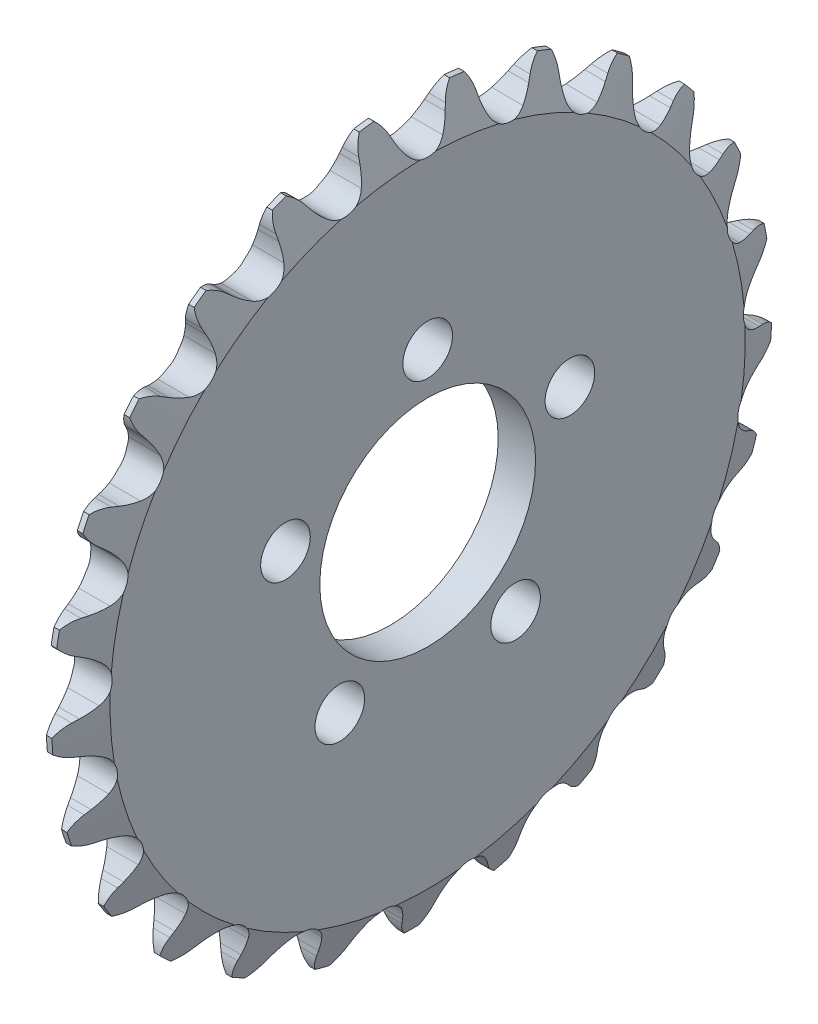
SolidWorks part; units mm, degrees
material "Alloy Steel"
ref_plane "Front Plane" through (0, 0, 0) normal (0, 0, 1) x (1, 0, 0)
ref_plane "Top Plane" through (0, 0, 0) normal (0, 1, 0) x (1, 0, 0)
ref_plane "Right Plane" through (0, 0, 0) normal (1, 0, 0) x (0, 0, -1)
ref_axis "X AXIS" through (-88.99, 0, 0) along (1, 0, 0)
ref_axis "Y AXIS" through (0, -55, 0) along (0, 1, 0)
ref_axis "Z AXIS" through (0, 0, 55) along (0, 0, -1)
other "Freeze***"
sketch "Sketch1" plane through (0, 0, 0) normal (1, 0, 0) x (0, 0, -1)
  line L0 (0, 25.3325) -> (-6.2999, 24.5366) construction
  line L1 (-1.9346, 25.3368) -> (-2.0951, 25.7414)
  line L2 (-1.9346, 25.3368) -> (2.0985, 26.9369) construction
  line L3 (2.0985, 26.9369) -> (0, 25.3325) construction
  line L4 (0, 25.3325) -> (-1.9329, 25.3325) construction
  line L5 (-3.4326, 27.1722) -> (-3.15, 24.9345) construction
  line L6 (0, 25.3325) -> (0, 23.6351) construction
  circle A0 centre (0, 0) radius 25.3325 construction
  arc A1 (-1.3484, 24.3015) -> (0, 23.6351) centre (0, 25.3325) ccw
  arc A2 (-1.3484, 24.3015) -> (-1.9346, 25.3368) centre (2.0985, 26.9369) cw
  arc A3 (-2.0951, 25.7414) -> (-3.4326, 27.1722) centre (-4.5863, 24.7531) ccw
sketch "Sketch2" plane through (0, 0, 0) normal (0, 0, 1) x (1, 0, 0)
  line L0 (0, 0) -> (0, 26.92) construction
  line L1 (-0.2064, 26.92) -> (0.2064, 26.92)
  line L2 (0.2064, 26.92) -> (1.397, 23.745)
  line L3 (1.397, 23.745) -> (1.397, 0)
  line L4 (-1.397, 0) -> (1.397, 0)
  line L5 (-1.397, 23.745) -> (-1.397, 0)
  line L6 (-0.2064, 26.92) -> (-1.397, 23.745)
  dimension "D1" = 26.92
  dimension "D2" = 2.794
revolve "Revolve1" add sketch "Sketch2" angle 360 about L4
sketch "Sketch3" plane through (0, 0, 0) normal (1, 0, 0) x (0, 0, -1)
  line L0 (-1.9346, 25.3368) -> (-2.0951, 25.7414) construction
  line L1 (-1.9346, 25.3368) -> (-2.0951, 25.7414)
  line L2 (0, 23.6351) -> (0, 0) construction
  line L3 (1.9346, 25.3368) -> (2.0951, 25.7414)
  arc A0 (-2.0951, 25.7414) -> (-3.4326, 27.1722) centre (-4.5863, 24.7531) ccw construction
  arc A1 (-1.9346, 25.3368) -> (-1.3484, 24.3015) centre (2.0985, 26.9369) ccw construction
  arc A2 (-1.3484, 24.3015) -> (0, 23.6351) centre (0, 25.3325) ccw construction
  arc A3 (-2.0951, 25.7414) -> (-3.4326, 27.1722) centre (-4.5863, 24.7531) ccw
  arc A4 (-1.9346, 25.3368) -> (-1.3484, 24.3015) centre (2.0985, 26.9369) ccw
  arc A5 (-1.3484, 24.3015) -> (1.3484, 24.3015) centre (0, 25.3325) ccw
  arc A6 (1.9346, 25.3368) -> (1.3484, 24.3015) centre (-2.0985, 26.9369) cw
  arc A7 (2.0951, 25.7414) -> (3.4326, 27.1722) centre (4.5863, 24.7531) cw
  arc A8 (-3.4326, 27.1722) -> (3.4326, 27.1722) centre (0, 0) cw
extrude "Cut-Extrude1" cut sketch "Sketch3" against normal through all both and the other way through all contours A8 A3 L1 A4 A5 A6 L3 A7 region at (0, 25.8551, 0)
pattern_circular "CirPattern1" count 25 over 360 about axis through (-88.99, 0, 0) along (1, 0, 0) of "Cut-Extrude1"
sketch "Sketch4" plane through (1.397, 0, 0) normal (1, 0, 0) x (0, 0, -1)
  line L0 (0, 0) -> (0, 11.176) construction
  circle A0 centre (0, 0) radius 8.0645
  circle A1 centre (0, 11.176) radius 1.8542
  circle A2 centre (10.629, 3.4536) radius 1.8542
  circle A3 centre (6.5691, -9.0416) radius 1.8542
  circle A4 centre (-6.5691, -9.0416) radius 1.8542
  circle A5 centre (-10.629, 3.4536) radius 1.8542
  point P15 (0, 0)
  dimension "D1" = 16.129
  dimension "D2" = 5
  dimension "D3" = 3.7084
  dimension "D4" = 11.176
extrude "Cut-Extrude2" cut sketch "Sketch4" against normal through all
sketch "Sketch5" plane through (-1.397, 0, 0) normal (-1, 0, 0) x (0, 0, 1)
  circle A0 centre (0, 0) radius 23.7837
equation "\"p\"= 2 / 8"
equation "\"n\"= 25"
equation "\"Dr\"= 0.13"
equation "\"Ds\"= 1.005 * \"Dr\" + 0.003"
equation "\"PD\"= \"p\" * cosec ( 180 / \"n\" )"
equation "\"A\"= 35 + 60 / \"n\""
equation "\"B\"= 18 - 56 / \"n\""
equation "\"ac\"= 0.8 * \"Dr\""
equation "\"ab\"= 1.4 * \"Dr\""
equation "\"D1@Sketch1\"=\"PD\""
equation "\"D2@Sketch1\"=\"p\""
equation "\"D3@Sketch1\"=\"Ds\""
equation "\"D4@Sketch1\"=\"A\""
equation "\"D5@Sketch1\"=\"B\""
equation "\"D6@Sketch1\"=\"ac\""
equation "\"D7@Sketch1\"=\"ab\""
equation "\"D1@Sketch2\"=(\"PD\"+\"p\"/2)/2"
equation "\"D4@Sketch2\"=\"p\"/2"
equation "\"D1@CirPattern1\"=\"n\""
